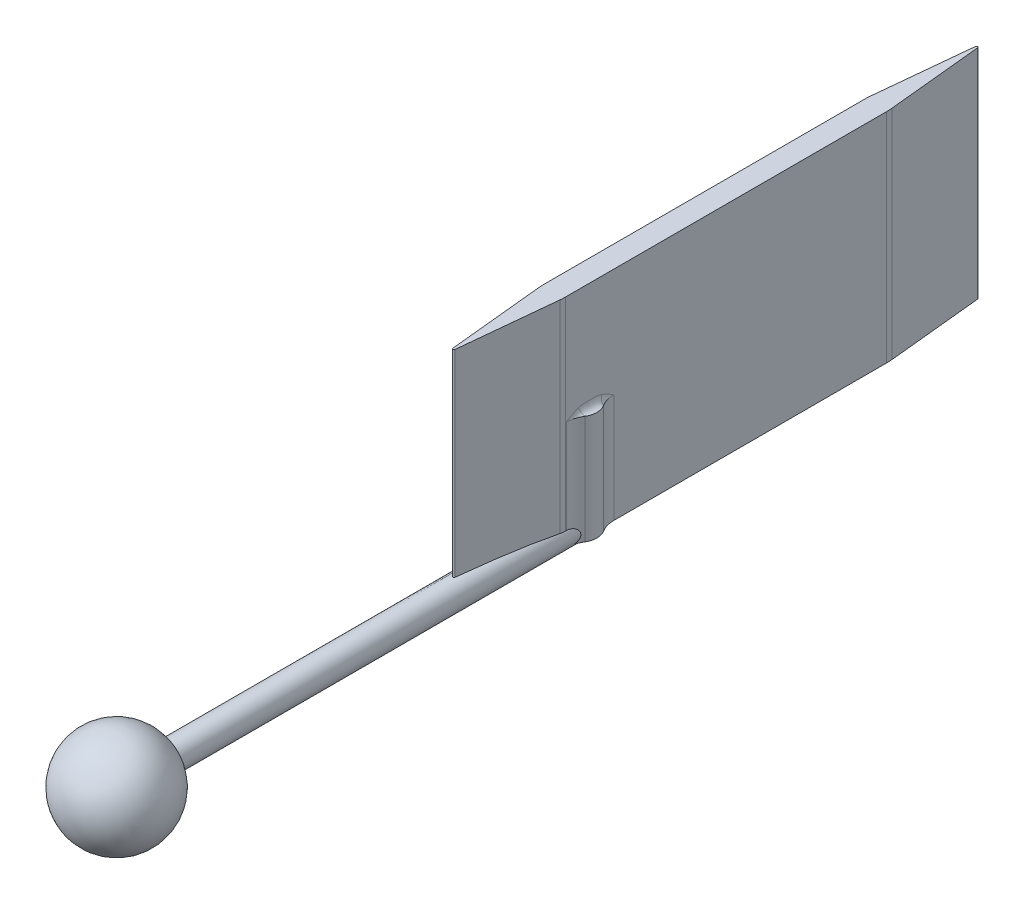
SolidWorks part; units mm, degrees
ref_plane "Front Plane" through (0, 0, 0) normal (0, 0, 1) x (1, 0, 0)
ref_plane "Top Plane" through (0, 0, 0) normal (0, 1, 0) x (1, 0, 0)
ref_plane "Right Plane" through (0, 0, 0) normal (1, 0, 0) x (0, 0, -1)
sketch "Sketch1" plane through (0, 0, 0) normal (0, 1, 0) x (1, 0, 0)
  line L0 (0, 0) -> (0, 127) construction
  line L1 (-2.54, 101.6) -> (-2.54, 25.4)
  line L2 (-2.54, 25.4) -> (-0.2527, 2.5274)
  line L3 (-2.54, 101.6) -> (-0.2527, 124.4726)
  line L4 (2.54, 25.4) -> (0.2527, 2.5274)
  line L5 (2.54, 101.6) -> (0.2527, 124.4726)
  line L6 (2.54, 101.6) -> (2.54, 25.4)
  arc A0 (-0.2527, 124.4726) -> (0.2527, 124.4726) centre (0, 124.4473) cw
  arc A1 (-0.2527, 2.5274) -> (0.2527, 2.5274) centre (0, 2.5527) ccw
  dimension "D5" = 0.254
  dimension "D1" = 25.4
  dimension "D2" = 127
  dimension "D3" = 25.4
  dimension "D4" = 2.54
extrude "Boss-Extrude1" add sketch "Sketch1" along normal blind 50.8
fillet "Fillet1" radius 12.7 4 edges at (-2.54, 25.4, -25.4) (-2.54, 25.4, -101.6) (2.54, 25.4, -25.4) (2.54, 25.4, -101.6)
sketch "Sketch3" plane through (0, 0, 0) normal (0, 0, 1) x (1, 0, 0)
  line L0 (0, 0) -> (0, 1.5875) construction
  circle A0 centre (0, 1.5875) radius 3.175
  dimension "D1" = 6.35
  dimension "D2" = 1.5875
extrude "Boss-Extrude2" add sketch "Sketch3" along normal blind 76.2 and the other way blind 31.75
sketch "Sketch4" plane through (0, 0, 0) normal (0, 1, 0) x (1, 0, 0)
  line L0 (0, 0) -> (0, 31.75) construction
  line L1 (-2.794, 0) -> (2.794, 0) construction
  circle A0 centre (0, 31.75) radius 3.175
  circle A1 centre (0, 31.75) radius 4.1275
  dimension "D1" = 6.35
  dimension "D3" = 8.255
  dimension "D2" = 31.75
sketch "Sketch5" plane through (0, 0, 0) normal (0, 1, 0) x (1, 0, 0)
extrude "Boss-Extrude3" add sketch "Sketch4" along normal blind 25.4 contours A1
extrude "Cut-Extrude1" cut sketch "Sketch4<3>" along normal blind 21.59 and the other way through all contours A0 region at (0, 0, -31.75)
sketch "Sketch4<3>" plane through (0, 0, 0) normal (0, 1, 0) x (1, 0, 0) same geometry as "Sketch4"
sketch "Sketch6" plane through (0, 0, 0) normal (1, 0, 0) x (0, 0, -1)
  line L0 (-76.2, 1.5875) -> (-76.2, 13.2715)
  line L1 (-76.2, 4.7625) -> (-76.2, -1.5875) construction
  line L2 (-76.2, -10.0965) -> (-76.2, 1.5875)
  arc A0 (-76.2, 13.2715) -> (-76.2, -10.0965) centre (-76.2, 1.5875) ccw
  dimension "D1" = 11.684
revolve "Revolve1" add sketch "Sketch6" angle 360 about L0
fillet "Fillet2" radius 6.35 4 edges at (2.54, 14.4463, -28.4966) (2.54, 12.7, -35.0034) (-2.54, 14.4463, -28.4966) (-2.54, 12.7, -35.0034)
fillet "Fillet3" radius 1.778 2 edges at (2.54, 25.4, -31.75) (-2.54, 25.4, -31.75)
